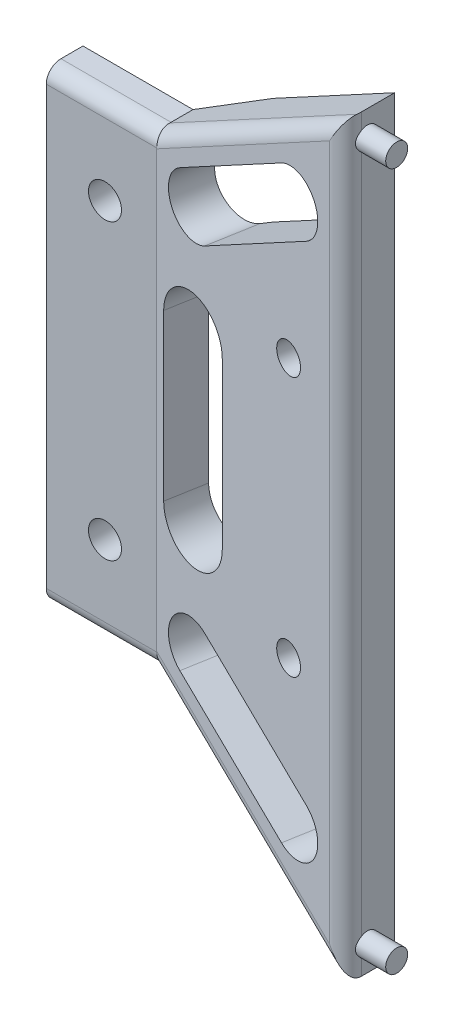
SolidWorks part; units mm, degrees
ref_plane "Front Plane" through (0, 0, 0) normal (0, 0, 1) x (1, 0, 0)
ref_plane "Top Plane" through (0, 0, 0) normal (0, 1, 0) x (1, 0, 0)
ref_plane "Right Plane" through (0, 0, 0) normal (1, 0, 0) x (0, 0, -1)
sketch "Sketch1" plane through (0, 0, 0) normal (0, 0, 1) x (1, 0, 0)
  line L0 (5, 31.75) -> (20, 31.75)
  line L1 (20, 31.75) -> (51, 51)
  line L2 (5, -31.75) -> (20, -31.75)
  line L3 (20, -31.75) -> (51, -51)
  line L4 (51, -51) -> (51, 51)
  line L7 (5, -31.75) -> (5, 31.75)
  line L8 (0, 0) -> (51, 0) construction
  point P7 (5, 0)
  dimension "D1" = 31.75
  dimension "D2" = 46
  dimension "D3" = 15
  dimension "D4" = 102
  dimension "D5" = 5
extrude "Boss-Extrude1" add sketch "Sketch1" along normal blind 12
sketch "Sketch3" plane through (0, 0, 0) normal (0, 1, 0) x (1, 0, 0)
  line L0 (5, -5) -> (20, -5)
  line L1 (5, -12) -> (5, 0) construction
  line L5 (20, 0) -> (20, 6.5) construction
  line L6 (5, 0) -> (20, 0) construction
  line L10 (20, -5) -> (51, -10.45)
  line L11 (51, -12) -> (51, 0) construction
  line L12 (52.5, -10.45) -> (51, -10.45) construction
  line L13 (51, -10.45) -> (51, -12)
  line L14 (51, -12) -> (5, -12)
  line L15 (5, -5) -> (5, -12)
  dimension "D1" = 5
extrude "Cut-Extrude1" cut sketch "Sketch3" against normal through all both and the other way through all
sketch "Sketch4" plane through (51, 0, 0) normal (1, 0, 0) x (0, 0, -1)
  circle A0 centre (-7.25, 47.55) radius 1.5
  circle A1 centre (-7.25, -47.55) radius 1.5
  dimension "D1" = 3
  dimension "D2" = 3
extrude "Boss-Extrude2" add sketch "Sketch4" along normal blind 4
ref_plane "Plane1" through (0, 0, -32.35) normal (0, 0, -1) x (-1, 0, 0)
sketch "Sketch5" plane through (0, 0, 5) normal (0, 0, 1) x (1, 0, 0)
  line L0 (5, -31.75) -> (5, 31.75) construction
  line L3 (13, 20) -> (13, -20) construction
  line L4 (0, 0) -> (51, 0) construction
  line L5 (51, -51) -> (51, 51) construction
  circle A0 centre (13, 20) radius 2.25
  circle A1 centre (13, -20) radius 2.25
  point P4 (13, 0)
  dimension "D1" = 4.5
  dimension "D3" = 4.5
  dimension "D2" = 40
  dimension "D4" = 8
extrude "Cut-Extrude2" cut sketch "Sketch5" against normal through all
fillet "Fillet1" radius 2 6 edges at (35.5, 41.375, 7.725) (12.5, 31.75, 5) (12.5, -31.75, 5) (35.5, -41.375, 7.725) (51, 0, 10.45) (51, 0, 0)
sketch "Sketch9" plane through (0, -31.75, 0) normal (0, -1, 0) x (-1, 0, 0)
  line L0 (-51, -3.5281) -> (-30.9317, 0)
  line L1 (-51, -8.0677) -> (-51, -2) construction
  line L2 (-20, 0) -> (-49, 0) construction
  line L3 (-50.9299, -8.5925) -> (-19.9905, -3.1532) construction
  line L4 (-30.9317, 0) -> (-51, 0)
  line L5 (-51, 0) -> (-51, -3.5281)
  dimension "D1" = 5
extrude "Cut-Extrude6" cut sketch "Sketch9" against normal through all both and the other way through all
sketch "Sketch10" plane through (-0.2531, 0, 1.4394) normal (-0.1732, 0, 0.9849) x (0.9849, 0, 0.1732)
  line L0 (43.6568, 36.7011) -> (26.5948, 26.2662) construction
  line L1 (45.7438, 33.2887) -> (28.6818, 22.8538)
  line L2 (41.5698, 40.1135) -> (24.5078, 29.6786)
  line L3 (49.6568, 47.4038) -> (20.5637, 29.6108) construction
  line L4 (49.6568, -47.4038) -> (49.6568, 47.4038) construction
  arc A0 (45.7438, 33.2887) -> (41.5698, 40.1135) centre (43.6568, 36.7011) ccw
  arc A1 (24.5078, 29.6786) -> (28.6818, 22.8538) centre (26.5948, 26.2662) ccw
  point P2 (35.1258, 31.4837)
  dimension "D3" = 20
  dimension "D4" = 6
  dimension "D1" = 8
  dimension "D2" = 6
extrude "Cut-Extrude7" cut sketch "Sketch10" against normal blind 10
mirror "Mirror2" about plane through (0, 0, 0) normal (0, 1, 0) of "Cut-Extrude7"
sketch "Sketch11" plane through (-0.2531, 0, 1.4394) normal (-0.1732, 0, 0.9849) x (0.9849, 0, 0.1732)
  line L0 (26.7084, 11.254) -> (26.7084, -11.254) construction
  line L1 (31.6266, 11.254) -> (31.6266, -11.254)
  line L2 (21.7902, 11.254) -> (21.7902, -11.254)
  line L3 (5.7902, -29.75) -> (5.7902, 29.75) construction
  line L5 (51.6266, 46.2925) -> (51.6266, -46.2925) construction
  arc A0 (31.6266, 11.254) -> (21.7902, 11.254) centre (26.7084, 11.254) ccw
  arc A1 (21.7902, -11.254) -> (31.6266, -11.254) centre (26.7084, -11.254) ccw
  point P2 (26.7084, 0)
  dimension "D1" = 16
  dimension "D2" = 20
  dimension "D3" = 22.508
extrude "Cut-Extrude8" cut sketch "Sketch11" against normal through all contours L1 A1 L2 A0
sketch "Sketch12" plane through (-0.2531, 0, 1.4394) normal (-0.1732, 0, 0.9849) x (0.9849, 0, 0.1732)
  circle A0 centre (42.7648, 17.7848) radius 2
  circle A1 centre (42.7648, -17.5986) radius 2
  dimension "D1" = 4
  dimension "D2" = 4
extrude "Cut-Extrude9" cut sketch "Sketch12" against normal blind 10
